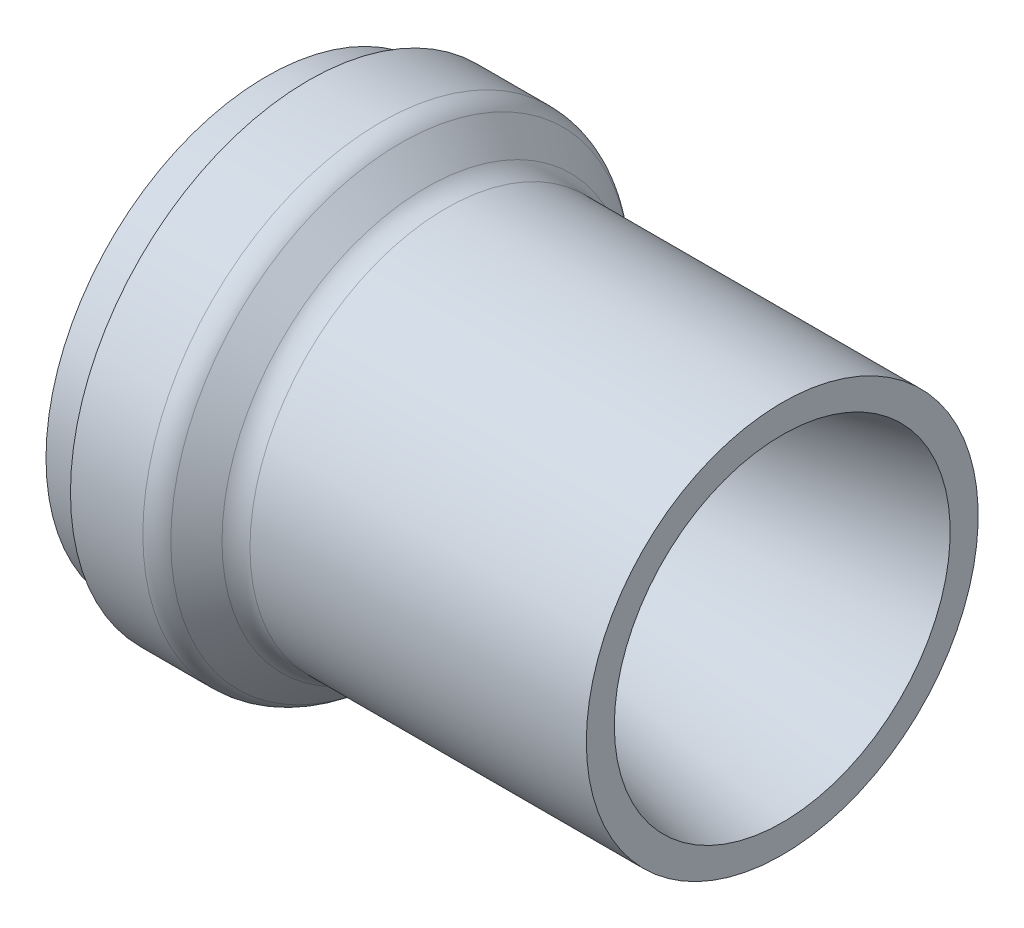
SolidWorks part; units mm, degrees
material "C (Graphite)"
ref_plane "Front Plane" through (0, 0, 0) normal (0, 0, 1) x (1, 0, 0)
ref_plane "Top Plane" through (0, 0, 0) normal (0, 1, 0) x (1, 0, 0)
ref_plane "Right Plane" through (0, 0, 0) normal (1, 0, 0) x (0, 0, -1)
sketch "Sketch1" plane through (0, 0, 0) normal (0, 0, 1) x (1, 0, 0)
  line L1 (117.0307, 12.446) -> (21.4326, 32.766)
  line L3 (0, 50.546) -> (76.2, 50.546) construction
  line L5 (15.0826, 32.766) -> (21.4326, 32.766)
  line L14 (0, 6.6421) -> (15.0826, 32.766)
  line L15 (30.4349, -1.5691) -> (36.2401, 4.2361)
  line L16 (40.7303, 6.096) -> (117.0307, 6.096)
  line L17 (117.0307, 6.096) -> (117.0307, 12.446)
  line L18 (25.9447, -3.429) -> (9.525, -3.429)
  line L19 (9.525, -3.429) -> (9.525, 0.5461)
  line L20 (0, 6.6421) -> (0, 0.5461)
  line L21 (0, 0.5461) -> (9.525, 0.5461)
  arc A2 (25.9447, -3.429) -> (30.4349, -1.5691) centre (25.9447, 2.921) ccw
  arc A3 (36.2401, 4.2361) -> (40.7303, 6.096) centre (40.7303, -0.254) cw
  point P13 (28.575, -3.429)
  point P16 (38.1, 6.096)
  dimension "D13" = 6.35
  dimension "D14" = 135
  dimension "D11" = 6.35
  dimension "D2" = 19.05
  dimension "D3" = 6.35
  dimension "D4" = 9.525
  dimension "D5" = 53.975
  dimension "D6" = 9.525
  dimension "D7" = 12
  dimension "D8" = 49.9999
  dimension "D9" = 17.78
  dimension "D10" = 60
  dimension "D12" = 38.1
revolve "Revolve1" add sketch "Sketch1" angle 360 about L3 region at (46.6214, 13.9838, 0)
